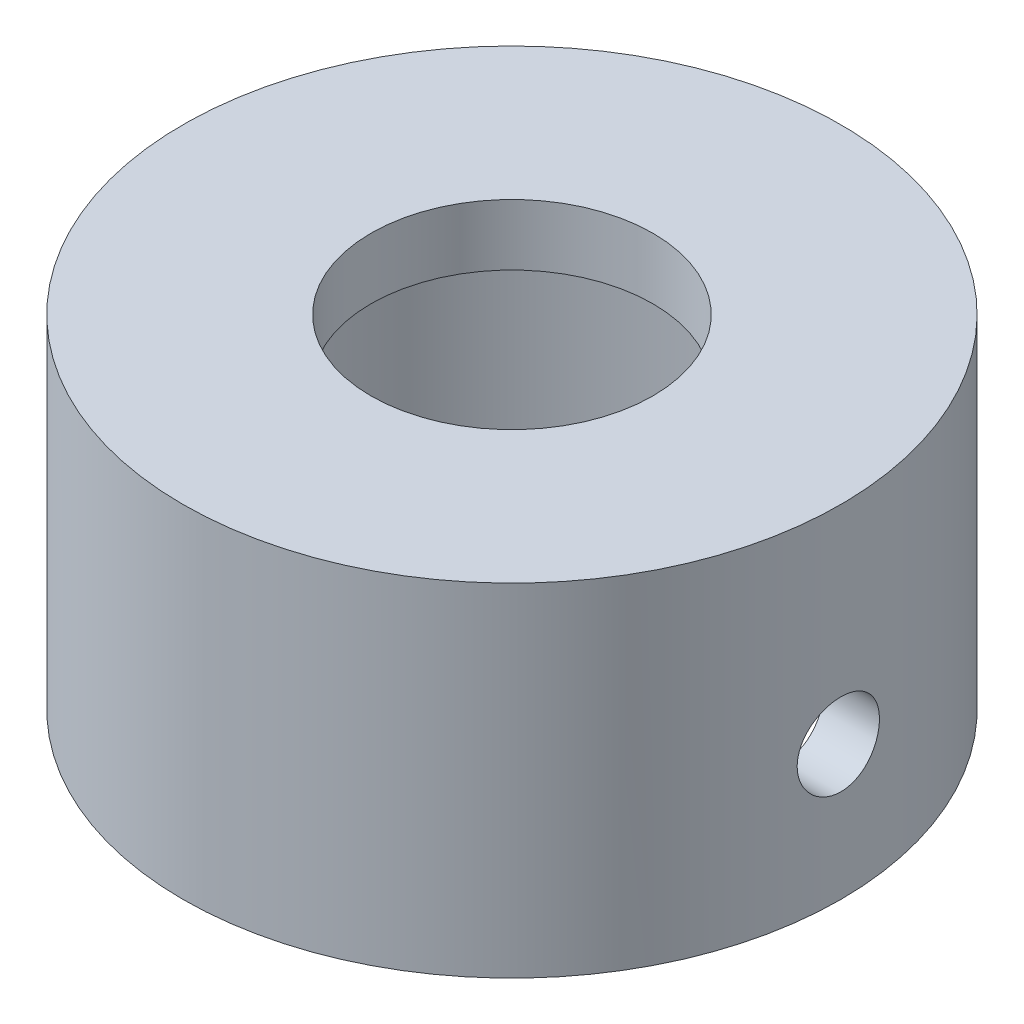
SolidWorks part; units mm, degrees
ref_plane "Front Plane" through (0, 0, 0) normal (0, 0, 1) x (1, 0, 0)
ref_plane "Top Plane" through (0, 0, 0) normal (0, 1, 0) x (1, 0, 0)
ref_plane "Right Plane" through (0, 0, 0) normal (1, 0, 0) x (0, 0, -1)
sketch "Sketch1" plane through (0, 0, 0) normal (0, 1, 0) x (1, 0, 0)
  circle A0 centre (0, 0) radius 22.225
  dimension "D2" = 44.45
extrude "Boss-Extrude1" add sketch "Sketch1" against normal blind 19.05
sketch "Sketch2" plane through (0, -19.05, 0) normal (0, -1, 0) x (1, 0, 0)
  circle A0 centre (0, 0) radius 18.542
  dimension "D1" = 37.084
extrude "Cut-Extrude1" cut sketch "Sketch2" against normal blind 13.3985
sketch "Sketch3" plane through (0, 0, 0) normal (0, 1, 0) x (1, 0, 0)
  circle A0 centre (0, 0) radius 9.525
  dimension "D1" = 19.05
extrude "Cut-Extrude2" cut sketch "Sketch3" against normal through all
sketch "Sketch4" plane through (0, -5.6515, 0) normal (0, -1, 0) x (1, 0, 0)
  circle A0 centre (0, 0) radius 15.875
  dimension "D1" = 31.75
extrude "Cut-Extrude3" cut sketch "Sketch4" against normal blind 1.524
sketch "Sketch5" plane through (0, 0, 0) normal (1, 0, 0) x (0, 0, -1)
  line L0 (-15.875, -4.1275) -> (15.875, -4.1275) construction
  circle A0 centre (0, -14.0335) radius 2.7781
  dimension "D1" = 5.5562
  dimension "D2" = 9.906
extrude "Cut-Extrude4" cut sketch "Sketch5" against normal through all and the other way through all
sketch "Sketch6" plane through (0, -19.05, 0) normal (0, -1, 0) x (1, 0, 0)
  circle A0 centre (0, 0) radius 22.225
extrude "Boss-Extrude2" add sketch "Sketch6" along normal blind 4.064
sketch "Sketch7" plane through (0, -23.114, 0) normal (0, -1, 0) x (1, 0, 0)
  circle A1 centre (0, 0) radius 18.542
  circle A2 centre (0, 0) radius 18.542 construction
  dimension "D1" = 0
extrude "Cut-Extrude5" cut sketch "Sketch7" against normal blind 6.35
